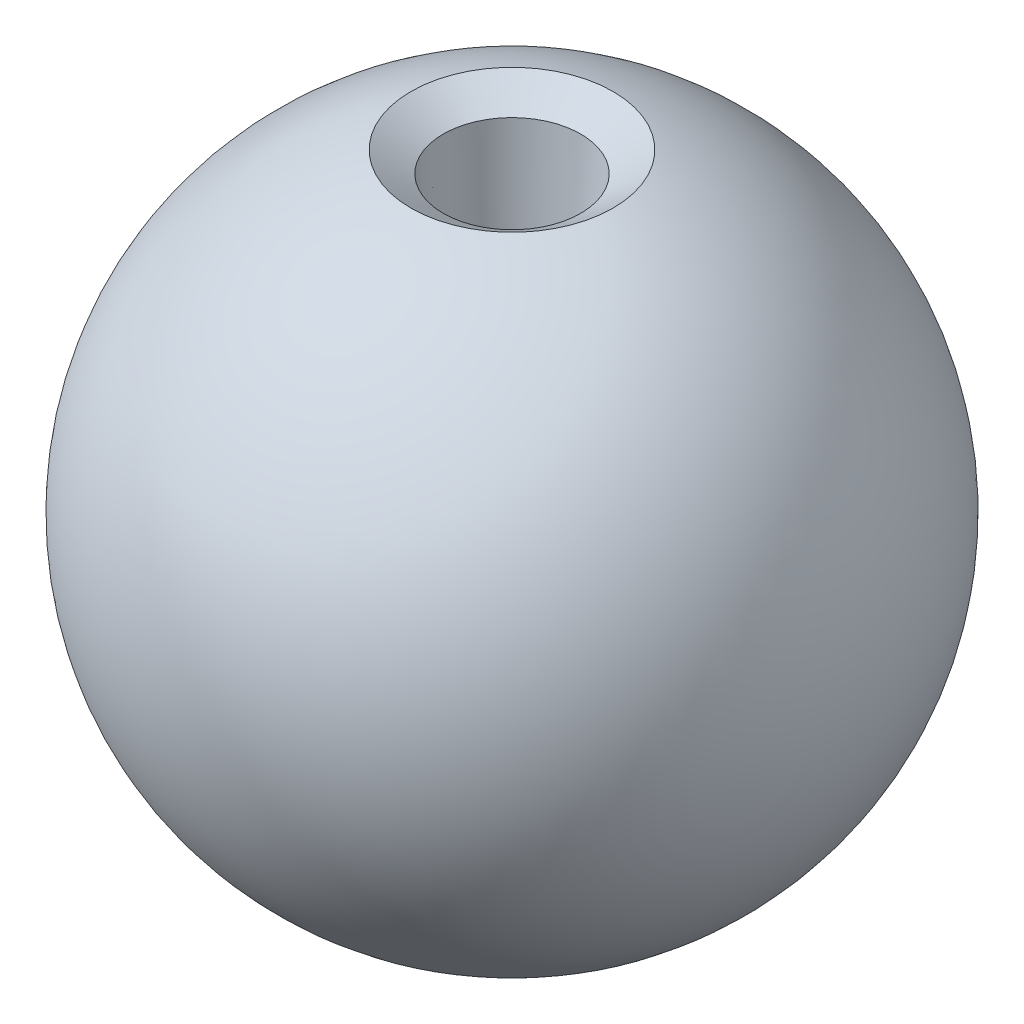
SolidWorks part; units mm, degrees
ref_plane "Front Plane" through (0, 0, 0) normal (0, 0, 1) x (1, 0, 0)
ref_plane "Top Plane" through (0, 0, 0) normal (0, 1, 0) x (1, 0, 0)
ref_plane "Right Plane" through (0, 0, 0) normal (1, 0, 0) x (0, 0, -1)
sketch "Sketch1" plane through (0, 0, 0) normal (1, 0, 0) x (0, 0, -1)
  line L0 (0, 0) -> (0, 10)
  line L1 (0, 0) -> (0, -10)
  arc A0 (0, -10) -> (0, 10) centre (0, 0) ccw
  dimension "D1" = 10
  dimension "D2" = 180
revolve "Revolve1" add sketch "Sketch1" angle 360 about L0
sketch "Sketch2" plane through (0, 0, 0) normal (1, 0, 0) x (0, 0, -1)
  line L0 (0, 0) -> (0, 10.64)
  line L1 (0, 10.64) -> (2.2, 10.64)
  line L2 (2.2, 10.64) -> (1.5, 0)
  line L3 (1.5, 0) -> (0, 0)
  dimension "D1" = 10.64
  dimension "D2" = 2.2
  dimension "D3" = 1.5
revolve "Cut-Revolve1" cut sketch "Sketch2" angle 360 about L0
chamfer "Chamfer1" distance 1 angle 45 1 edges at (0, 9.7678, -2.1426) first distance on face at (0, 9.7678, -2.1426)
